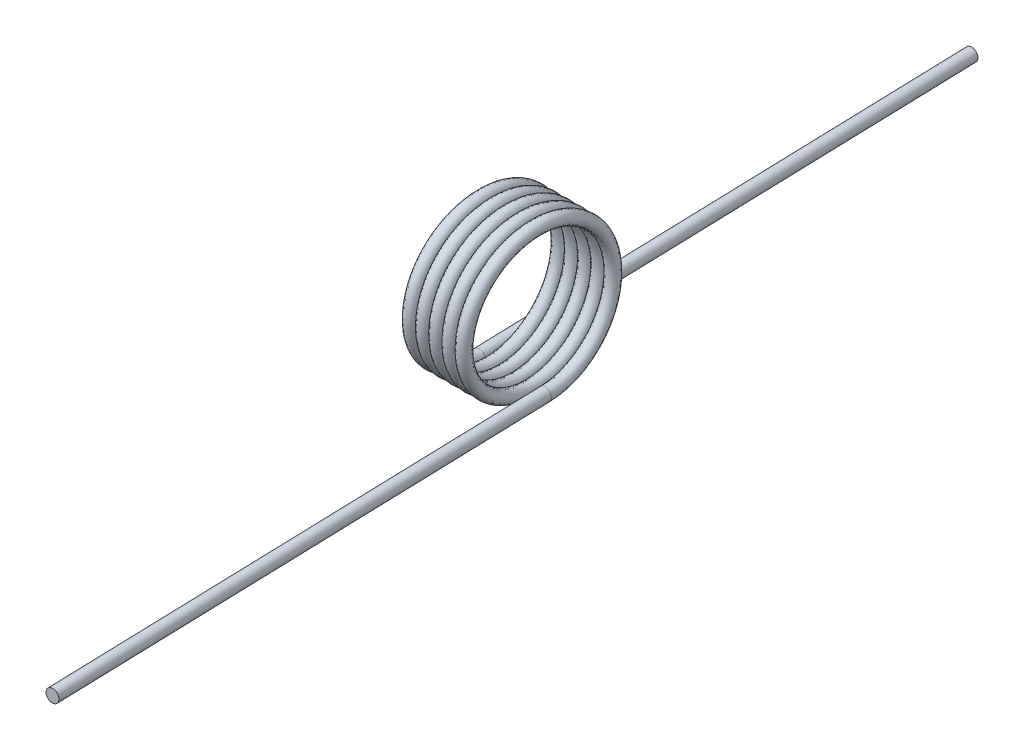
SolidWorks part; units mm, degrees
note: '?' marks a value the reader was unsure of.
ref_plane "xy_plane" through (0, 0, 0) normal (0, 0, 1) x (1, 0, 0)
ref_plane "zx_plane" through (0, 0, 0) normal (0, 1, 0) x (1, 0, 0)
ref_plane "yz_plane" through (0, 0, 0) normal (1, 0, 0) x (0, 0, -1)
ref_axis "x_axis" through (-1.3397, 0, 0) along (1, 0, 0)?
ref_axis "y_axis" through (0, -4.2648, 0) along (0, 1, 0)?
ref_axis "z_axis" through (0, 0, -27.9381) along (0, 0, 1)?
sketch "Sketch1" plane through (0, 0, 0) normal (1, 0, 0) x (0, 0, -1)
  line L0 (0, 0) -> (0, -3.2385) construction
  line L1 (0, -3.2385) -> (0, -3.556) construction
  line L2 (0, -3.556) -> (0, -3.8735) construction
  circle A0 centre (0, 0) radius 3.2385 construction
  circle A1 centre (0, 0) radius 3.8735 construction
  circle A2 centre (0, 0) radius 3.556
  circle A3 centre (0, -3.556) radius 0.3175 construction
  circle A4 centre (0, 0) radius 2.5781 construction
curve "Helix/Spiral1" pitch 0.6604 height 3.302 turns 5
ref_plane "Plane1" through (0, -3.556, 0) normal (0.0295, 0, 0.9996) x (0.9996, 0, -0.0295)
sketch "Sketch2" plane through (0, -3.556, 0) normal (0.0295, 0, 0.9996) x (0.9996, 0, -0.0295)
  circle A0 centre (0, 0) radius 0.3175
  dimension "D1" = 0.635
sweep "Sweep1" add profiles "Sketch2" path "Helix/Spiral1"
sketch "Sketch3" plane through (0, 0, 0) normal (-0.0295, 0, -0.9996) x (-0.9996, 0, 0.0295)
  circle A1 centre (0, -3.556) radius 0.3175
  circle A2 centre (0, -3.556) radius 0.3175
  dimension "D1" = 0
extrude "Extrude1" add sketch "Sketch3" along normal blind 25.4
sketch "Sketch4" plane through (0.0029, 0, 0.0975) normal (0.0295, 0, 0.9996) x (0.9959, -0.0856, -0.0294)
  circle A1 centre (3.5928, -3.2604) radius 0.3175
  circle A2 centre (3.5928, -3.2604) radius 0.3175
  dimension "D1" = 0
extrude "Extrude2" add sketch "Sketch4" along normal blind 25.4
sketch "Sketch5" plane through (0, 0, 0) normal (1, 0, 0) x (0, 0, -1)
  circle A0 centre (0, 0) radius 2.5781 construction
  circle A1 centre (0, 0) radius 2.5781
equation "\"D4@Helix/Spiral1\"=\"Wire Dia@Sketch1\"+.001"
equation "\"D1@Sketch2\"=\"Wire Dia@Sketch1\""
equation "\"D1@Extrude2\"=\"Leg Length@Extrude1\""
